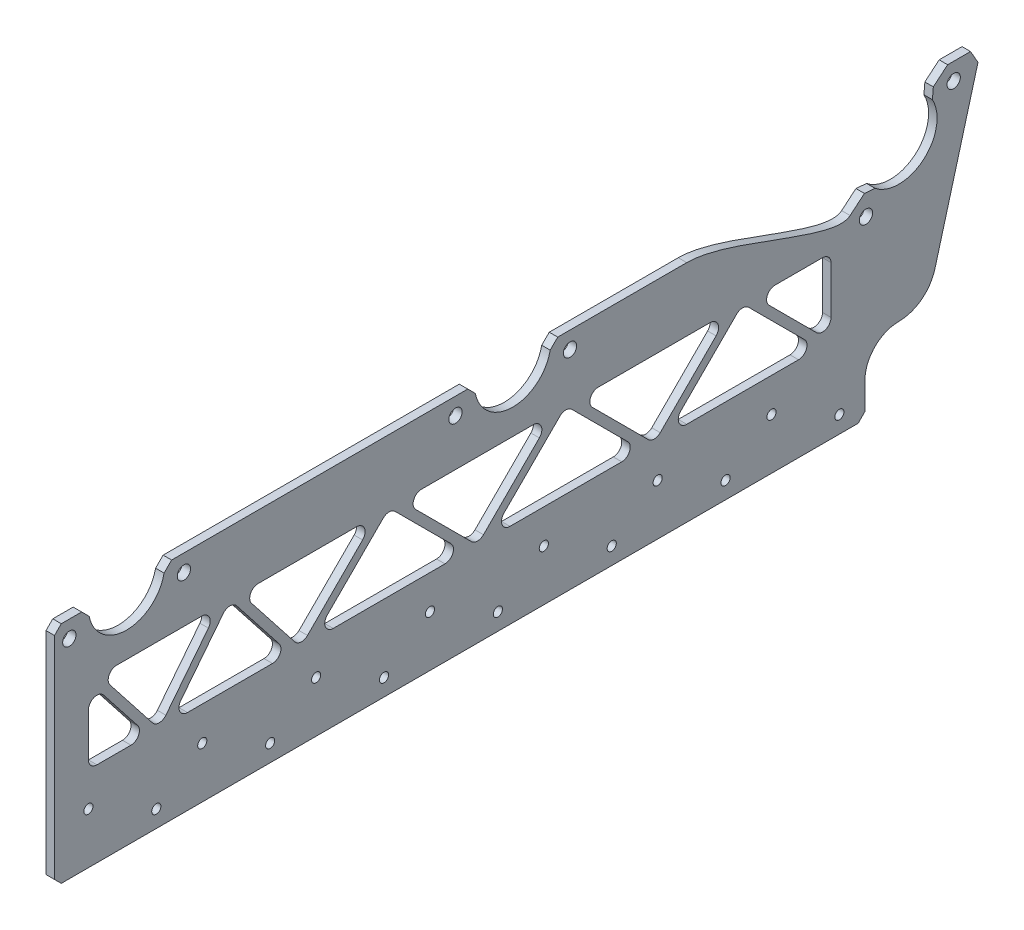
SolidWorks part; units mm, degrees
material "6061 Alloy"
ref_plane "Front Plane" through (0, 0, 0) normal (0, 0, 1) x (1, 0, 0)
ref_plane "Top Plane" through (0, 0, 0) normal (0, 1, 0) x (1, 0, 0)
ref_plane "Right Plane" through (0, 0, 0) normal (1, 0, 0) x (0, 0, -1)
sketch "Sketch1" plane through (0, 0, 0) normal (1, 0, 0) x (0, 0, -1)
  line L0 (-12.7, -12.7) -> (-315.9125, -12.7)
  line L1 (-315.9125, -12.7) -> (-315.9125, 71.4375)
  line L2 (-315.9125, 71.4375) -> (-303.2125, 71.4375)
  line L3 (-274.6375, 71.4375) -> (-158.75, 71.4375)
  line L5 (10.9449, 80.6213) -> (18.2432, 86.7453)
  line L7 (-315.9125, 12.7) -> (13.4735, 12.7) construction
  line L8 (-12.7, -12.7) -> (-12.7, 0)
  line L9 (0, 12.4079) -> (0, 12.7) construction
  line L10 (13.4735, 22.9788) -> (30.9432, 86.7453)
  line L12 (-10.9449, 62.2537) -> (10.9449, 80.6213) construction
  line L13 (18.2432, 86.7453) -> (30.9432, 86.7453)
  line L14 (-130.175, 71.4375) -> (-79.375, 71.4375)
  line L15 (-10.9449, 62.2537) -> (-18.2432, 56.1297)
  line L16 (-315.9125, 15.875) -> (13.4735, 15.875) construction
  line L17 (-288.925, 71.4375) -> (-144.4625, 71.4375) construction
  line L18 (0, 71.4375) -> (-144.4625, 71.4375) construction
  arc A3 (0, 12.7) -> (13.4735, 22.9788) centre (0, 26.67) ccw
  arc A4 (0, 12.7) -> (-12.7, 0) centre (0, 0) ccw
  circle A5 centre (0, 0) radius 12.4079 construction
  arc A6 (-303.2125, 71.4375) -> (-274.6375, 71.4375) centre (-288.925, 71.4375) ccw
  arc A7 (-158.75, 71.4375) -> (-130.175, 71.4375) centre (-144.4625, 71.4375) ccw
  arc A8 (-10.9449, 62.2537) -> (10.9449, 80.6213) centre (0, 71.4375) ccw
  spline S0 degree 3 poles (-18.2432, 56.1297) (-24.729, 50.6874) (-62.4417, 71.4375) (-79.375, 71.4375) knots 0 0 0 0 1 1 1 1
  point P4 (-164.3062, -12.7)
  dimension "D1" = 25.4
  dimension "D3" = 12.7
  dimension "D5" = 28.575
  dimension "D6" = 41.275
  dimension "D7" = 13.97
  dimension "D8" = 12.7
  dimension "D10" = 24.8158
  dimension "D13" = 9.5273
  dimension "D14" = 140
  dimension "D15" = 50.8
  dimension "D16" = 50.8
  dimension "D17" = 25.4
  dimension "D2" = 0
  dimension "D4" = 12.7
  dimension "D9" = 12.7
  dimension "D11" = 288.925
  dimension "D12" = 288.925
  dimension "D18" = 3.175
extrude "Boss-Extrude1" add sketch "Sketch1" along normal blind 3.175
hole_wizard "#10 Clearance Hole1" positions "Sketch2" profile "Sketch3" hole size "#10" standard "ANSI Inch" end condition through all
sketch "Sketch2" plane through (3.175, 0, 0) normal (1, 0, 0) x (0, 0, -1)
  line L0 (-310.3562, 65.0875) -> (-267.4937, 65.0875) construction
  line L2 (-165.8938, 65.0875) -> (-123.0312, 65.0875) construction
  line L4 (-12.3356, 52.7974) -> (20.499, 80.3489) construction
  line L6 (-303.2125, 71.4375) -> (-315.9125, 71.4375) construction
  line L7 (-288.925, 65.0875) -> (-288.925, 71.4375) construction
  line L9 (-144.4625, 71.4375) -> (-144.4625, 65.0875) construction
  line L11 (0, 71.4375) -> (4.0817, 66.5731) construction
  line L14 (18.2432, 86.7453) -> (10.9449, 80.6213) construction
  line L15 (18.2432, 86.7453) -> (10.9449, 80.6213) construction
  point P0 (-310.3562, 65.0875)
  point P2 (-267.4937, 65.0875)
  point P4 (-165.8938, 65.0875)
  point P6 (-123.0312, 65.0875)
  point P8 (-12.3356, 52.7974)
  point P10 (20.499, 80.3489)
  dimension "D1" = 42.8625
  dimension "D2" = 6.35
  dimension "D3" = 6.35
sketch "Sketch3" plane through (3.175, 65.0875, 310.3562) normal (0, 1, 0) x (0, 0, -1)
  line L0 (0, 0) -> (0, 3.175)
  line L1 (0, 3.175) -> (2.4892, 3.175)
  line L2 (2.4892, 3.175) -> (2.4892, 0)
  line L5 (2.4892, 0) -> (0, 0)
  line L11 (0, -6.35) -> (0, 107.95) construction
  dimension "Thru Hole Dia." = 4.9784
  dimension "Thru Hole Depth" = 3.175
chamfer "Chamfer1" distance 5.08 angle 45 1 edges at (1.5875, 86.7453, -30.9432) first distance on face at (1.5875, 54.862, -22.2083)
hole_wizard "1/8 (0.135) Diameter Hole1" positions "Sketch4" profile "Sketch5" hole size "1/8" standard "ANSI Inch"
sketch "Sketch4" plane through (3.175, 0, 0) normal (1, 0, 0) x (0, 0, -1)
  line L0 (-315.9125, -12.7) -> (-12.7, -12.7) construction
  line L1 (-12.7, -12.7) -> (-12.7, 0) construction
  line L2 (-315.9125, 71.4375) -> (-315.9125, -12.7) construction
  point P0 (-22.2504, -6.35)
  point P2 (-47.6504, 6.35)
  point P14 (-64.8441, -6.35)
  point P15 (-90.2441, 6.35)
  point P16 (-107.4378, -6.35)
  point P17 (-132.8378, 6.35)
  point P18 (-150.0314, -6.35)
  point P19 (-175.4315, 6.35)
  point P20 (-192.6251, -6.35)
  point P21 (-218.0251, 6.35)
  point P22 (-235.2188, -6.35)
  point P23 (-260.6188, 6.35)
  point P24 (-277.8125, -6.35)
  point P25 (-303.2125, 6.35)
  dimension "D1" = 6.35
  dimension "D2" = 9.5504
  dimension "D3" = 12.7
  dimension "D4" = 25.4
  dimension "D6" = 12.7
  dimension "D5" = 7
sketch "Sketch5" plane through (3.175, -6.35, 22.2504) normal (0, 1, 0) x (0, 0, -1)
  line L0 (0, 0) -> (0, 17.5402)
  line L1 (0, 17.5402) -> (1.7145, 16.51)
  line L2 (1.7145, 16.51) -> (1.7145, 0)
  line L5 (1.7145, 0) -> (0, 0)
  line L10 (0, 17.5402) -> (-1.7145, 16.51) construction
  line L11 (0, -6.35) -> (0, 107.95) construction
  dimension "Hole Dia." = 3.429
  dimension "Hole Depth" = 16.51
  dimension "Drill Angle" = 118
sketch "Sketch6" plane through (3.175, 0, 0) normal (1, 0, 0) x (0, 0, -1)
  line L0 (-303.2125, 47.625) -> (-303.2125, 19.05)
  line L1 (-303.2125, 19.05) -> (-280.7754, 19.05)
  line L2 (-280.7754, 19.05) -> (-303.2125, 47.625)
  line L3 (-315.9125, 12.7) -> (-12.7, 12.7) construction
  line L4 (-315.9125, 71.4375) -> (-315.9125, -12.7) construction
  line L5 (-315.9125, -12.7) -> (-12.7, -12.7) construction
  line L6 (-315.9125, 15.875) -> (-12.7, 15.875) construction
  line L7 (-299.1757, 47.625) -> (-276.7386, 19.05)
  line L8 (-276.7386, 19.05) -> (-254.3015, 47.625)
  line L9 (-254.3015, 47.625) -> (-299.1757, 47.625)
  line L10 (-272.7018, 19.05) -> (-250.2647, 47.625)
  line L11 (-250.2647, 47.625) -> (-227.8276, 19.05)
  line L12 (-227.8276, 19.05) -> (-272.7018, 19.05)
  line L13 (-246.2279, 47.625) -> (-223.7908, 19.05)
  line L14 (-223.7908, 19.05) -> (-195.2158, 47.625)
  line L15 (-195.2158, 47.625) -> (-246.2279, 47.625)
  line L16 (-219.3006, 19.05) -> (-190.7256, 47.625)
  line L17 (-190.7256, 47.625) -> (-162.1506, 19.05)
  line L18 (-162.1506, 19.05) -> (-219.3006, 19.05)
  line L19 (-186.2355, 47.625) -> (-157.6605, 19.05)
  line L20 (-157.6605, 19.05) -> (-129.0855, 47.625)
  line L21 (-129.0855, 47.625) -> (-186.2355, 47.625)
  line L22 (-124.5954, 47.625) -> (-153.1704, 19.05)
  line L23 (-153.1704, 19.05) -> (-96.0204, 19.05)
  line L24 (-96.0204, 19.05) -> (-124.5954, 47.625)
  line L25 (-120.1053, 47.625) -> (-91.5303, 19.05)
  line L26 (-91.5303, 19.05) -> (-62.9553, 47.625)
  line L27 (-62.9553, 47.625) -> (-120.1053, 47.625)
  line L28 (-58.4651, 47.625) -> (-87.0401, 19.05)
  line L29 (-87.0401, 19.05) -> (-29.8901, 19.05)
  line L30 (-29.8901, 19.05) -> (-58.4651, 47.625)
  line L31 (-12.7, -12.7) -> (-12.7, 0) construction
  line L32 (-53.975, 47.625) -> (-25.4, 19.05)
  line L33 (-25.4, 19.05) -> (-25.4, 47.625)
  line L34 (-25.4, 47.625) -> (-53.975, 47.625)
  arc A0 (-303.2125, 71.4375) -> (-274.6375, 71.4375) centre (-288.925, 71.4375) ccw construction
  dimension "D15" = 9.525
  dimension "D1" = 25.4
  dimension "D3" = 3.175
  dimension "D4" = 12.7
  dimension "D5" = 3.175
  dimension "D6" = 3.175
  dimension "D7" = 3.175
  dimension "D8" = 3.175
  dimension "D9" = 3.175
  dimension "D10" = 3.175
  dimension "D11" = 3.175
  dimension "D12" = 3.175
  dimension "D13" = 3.175
  dimension "D14" = 12.7
  dimension "D2" = 3.175
extrude "Cut-Extrude1" cut sketch "Sketch6" against normal through all
fillet "Fillet1" radius 3.175 30 edges at (1.5875, 19.05, 25.4) (1.5875, 47.625, 53.975) (1.5875, 47.625, 25.4) (1.5875, 19.05, 162.1506) (1.5875, 19.05, 219.3006) (1.5875, 19.05, 91.5303) (1.5875, 47.625, 120.1053) (1.5875, 47.625, 62.9553) (1.5875, 19.05, 87.0401) (1.5875, 47.625, 58.4651) (1.5875, 19.05, 29.8901) (1.5875, 19.05, 157.6605) (1.5875, 47.625, 186.2355) (1.5875, 47.625, 129.0855) (1.5875, 19.05, 153.1704) (1.5875, 47.625, 124.5954) (1.5875, 19.05, 96.0204) (1.5875, 47.625, 190.7256) (1.5875, 19.05, 223.7908) (1.5875, 47.625, 246.2279) (1.5875, 47.625, 195.2158) (1.5875, 19.05, 227.8276) (1.5875, 19.05, 272.7018) (1.5875, 47.625, 250.2647) (1.5875, 19.05, 276.7386) (1.5875, 47.625, 299.1757) (1.5875, 47.625, 254.3015) (1.5875, 19.05, 303.2125) (1.5875, 19.05, 280.7754) (1.5875, 47.625, 303.2125)
chamfer "Chamfer2" distance 2.54 angle 45 9 edges at (1.5875, -12.7, 12.7) (1.5875, -12.7, 315.9125) (1.5875, 71.4375, 315.9125) (1.5875, 80.6213, -10.9449) (1.5875, 62.2537, 10.9449) (1.5875, 71.4375, 130.175) (1.5875, 71.4375, 158.75) (1.5875, 71.4375, 274.6375) (1.5875, 71.4375, 303.2125)
